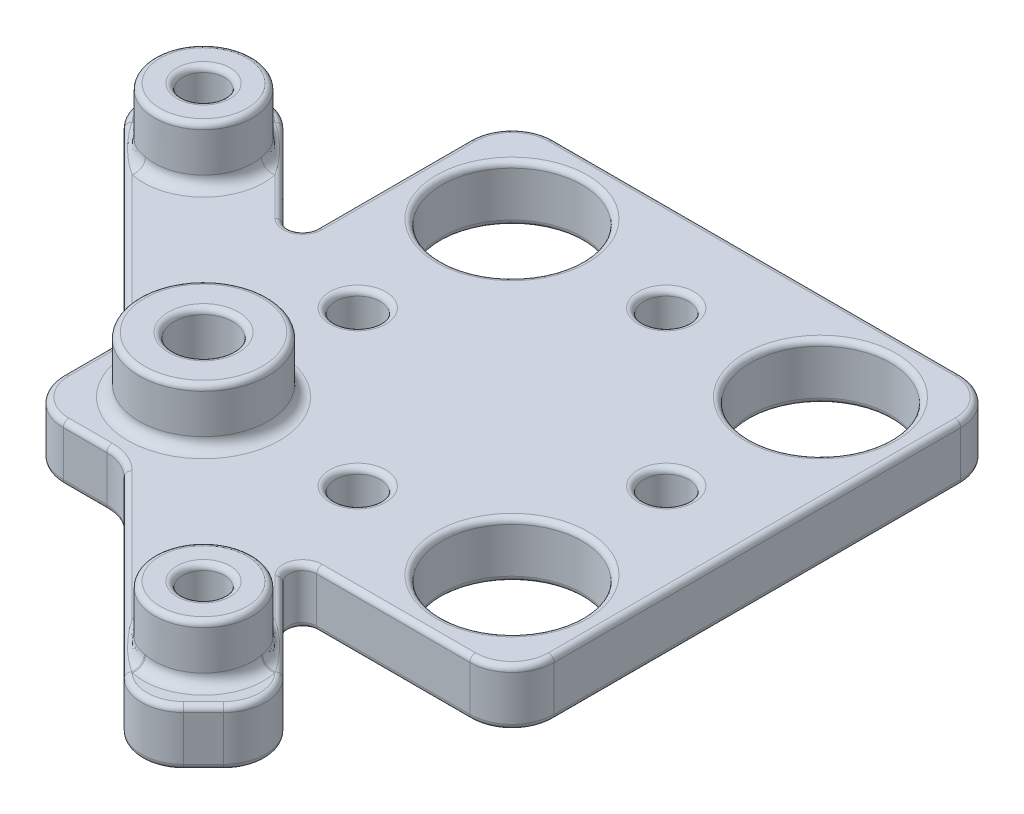
SolidWorks part; units mm, degrees
ref_plane "Front Plane" through (0, 0, 0) normal (0, 0, 1) x (1, 0, 0)
ref_plane "Top Plane" through (0, 0, 0) normal (0, 1, 0) x (1, 0, 0)
ref_plane "Right Plane" through (0, 0, 0) normal (1, 0, 0) x (0, 0, -1)
sketch "Sketch1" plane through (0, 0, 0) normal (0, 1, 0) x (1, 0, 0)
  line L0 (-15.4203, -12.2365) -> (0, -27.6569)
  line L1 (0, 0) -> (35, 0)
  line L2 (0, 0) -> (0, -16.3431)
  line L3 (0, -35) -> (7.3431, -35)
  line L4 (35, 0) -> (35, -35)
  line L5 (22.7635, -50.4203) -> (28.4203, -44.7635)
  line L6 (28.4203, -44.7635) -> (18.6569, -35)
  line L7 (-15.4203, -12.2365) -> (-9.7635, -6.5797)
  line L8 (0, -16.3431) -> (-9.7635, -6.5797)
  line L9 (18.6569, -35) -> (35, -35)
  line L10 (0, -27.6569) -> (0, -35)
  line L11 (7.3431, -35) -> (22.7635, -50.4203)
  circle A0 centre (28.5, -6.5) radius 5
  circle A1 centre (6.5, -6.5) radius 5
  circle A2 centre (6.5, -28.5) radius 5 construction
  circle A3 centre (28.5, -28.5) radius 5
  circle A4 centre (17.5, -28.5) radius 1.6
  circle A5 centre (17.5, -17.5) radius 3.6254 construction
  circle A6 centre (6.5, -17.5) radius 1.6
  circle A7 centre (17.5, -6.5) radius 1.6
  circle A8 centre (28.5, -17.5) radius 1.6
  circle A9 centre (6.5, -28.5) radius 2.1
  circle A10 centre (-8.8796, -13.1204) radius 1.5
  circle A11 centre (21.8796, -43.8796) radius 1.5
  point P26 (17.5, -17.5)
  dimension "D3" = 10
  dimension "D8" = 3.2
  dimension "D12" = 4.2
  dimension "D17" = 3
  dimension "D18" = 3
  dimension "D1" = 35
  dimension "D2" = 35
  dimension "D4" = 6.5
  dimension "D5" = 6.5
  dimension "D9" = 6.5
  dimension "D10" = 17.5
  dimension "D13" = 54
  dimension "D14" = 8
  dimension "D15" = 27
  dimension "D16" = 4
  dimension "D19" = 4
  dimension "D20" = 4
  dimension "D21" = 21.75
  dimension "D22" = 21.75
  dimension "D6" = 2
  dimension "D7" = 2
  dimension "D11" = 4
extrude "Boss-Extrude1" add sketch "Sketch1" along normal blind 4
fillet "Fillet3" radius 3 8 edges at (0, 2, 0) (35, 2, 0) (28.4203, 2, 44.7635) (-9.7635, 2, 6.5797) (22.7635, 2, 50.4203) (-15.4203, 2, 12.2365) (35, 2, 35) (0, 2, 35)
fillet "Fillet4" radius 3 2 edges at (7.3431, 2, 35) (0, 2, 27.6569)
fillet "Fillet5" radius 1 2 edges at (18.6569, 2, 35) (0, 2, 16.3431)
fillet "Fillet6" radius 0.4 3 edges at (28.5, 4, 33.5) (28.5, 4, 11.5) (6.5, 4, 11.5)
fillet "Fillet7" radius 0.4 24 edges at (34.1213, 4, 0.8787) (35, 4, 17.5) (34.1213, 4, 34.1213) (26.5355, 4, 35) (20.1472, 4, 35.6173) (23.3315, 4, 39.6746) (27.1777, 4, 44.7635) (25.5919, 4, 47.5919) (22.7635, 4, 49.1777) (14.432, 4, 42.0888) (7.2486, 4, 35.2284) (4.5503, 4, 35) (0.8787, 4, 34.1213) (0, 4, 30.4497) (-0.2284, 4, 27.7514) (-7.0888, 4, 20.568) (-14.1777, 4, 12.2365) (-12.5919, 4, 9.4081) (-9.7635, 4, 7.8223) (-4.6746, 4, 11.6685) (-0.6173, 4, 14.8528) (0, 4, 8.4645) (0.8787, 4, 0.8787) (17.5, 4, 0)
sketch "Sketch2" plane through (0, 4, 0) normal (0, 1, 0) x (1, 0, 0)
  circle A1 centre (-8.8796, -13.1204) radius 3.5
  circle A2 centre (-8.8796, -13.1204) radius 1.5
  circle A3 centre (-8.8796, -13.1204) radius 1.5
  circle A6 centre (21.8796, -43.8796) radius 3.5
  circle A7 centre (21.8796, -43.8796) radius 3.5
  circle A10 centre (21.8796, -43.8796) radius 1.5
  circle A11 centre (21.8796, -43.8796) radius 1.5
  circle A12 centre (6.5, -28.5) radius 4.6
  circle A13 centre (6.5, -28.5) radius 2.1
  circle A14 centre (6.5, -28.5) radius 2.1
  dimension "D1" = 0
  dimension "D2" = 2
  dimension "D3" = 2
  dimension "D4" = 0
  dimension "D5" = 0
  dimension "D6" = 2.5
extrude "Boss-Extrude2" add sketch "Sketch2" along normal blind 4
fillet "Fillet8" radius 0.4 3 edges at (21.8796, 8, 45.3796) (-8.8796, 8, 14.6204) (6.5, 8, 30.6)
fillet "Fillet9" radius 0.4 3 edges at (21.8796, 8, 47.3796) (6.5, 8, 33.1) (-8.8796, 8, 16.6204)
fillet "Fillet10" radius 0.8 3 edges at (21.8796, 4, 47.3796) (6.5, 4, 33.1) (-8.8796, 4, 16.6204)
fillet "Fillet11" radius 0.4 34 edges at (21.8796, 0, 45.3796) (-8.8796, 0, 14.6204) (6.5, 0, 19.1) (6.5, 0, 30.6) (17.5, 0, 30.1) (28.5, 0, 33.5) (28.5, 0, 19.1) (28.5, 0, 11.5) (6.5, 0, 11.5) (17.5, 0, 8.1) (7.2486, 0, 35.2284) (4.5503, 0, 35) (0.8787, 0, 34.1213) (0, 0, 30.4497) (-0.2284, 0, 27.7514) (-7.0888, 0, 20.568) (-14.1777, 0, 12.2365) (-12.5919, 0, 9.4081) (-9.7635, 0, 7.8223) (-4.6746, 0, 11.6685) (-0.6173, 0, 14.8528) (0, 0, 8.4645) (0.8787, 0, 0.8787) (17.5, 0, 0) (34.1213, 0, 0.8787) (35, 0, 17.5) (34.1213, 0, 34.1213) (26.5355, 0, 35) (20.1472, 0, 35.6173) (23.3315, 0, 39.6746) (27.1777, 0, 44.7635) (25.5919, 0, 47.5919) (22.7635, 0, 49.1777) (14.432, 0, 42.0888)
fillet "Fillet12" radius 0.4 4 edges at (17.5, 4, 8.1) (28.5, 4, 19.1) (17.5, 4, 30.1) (6.5, 4, 19.1)
equation "\"D4@Sketch1\"=6.5"
equation "\"D9@Sketch1\"=\"D5@Sketch1\""
equation "\"D10@Sketch1\"=\"D1@Sketch1\"/2"
